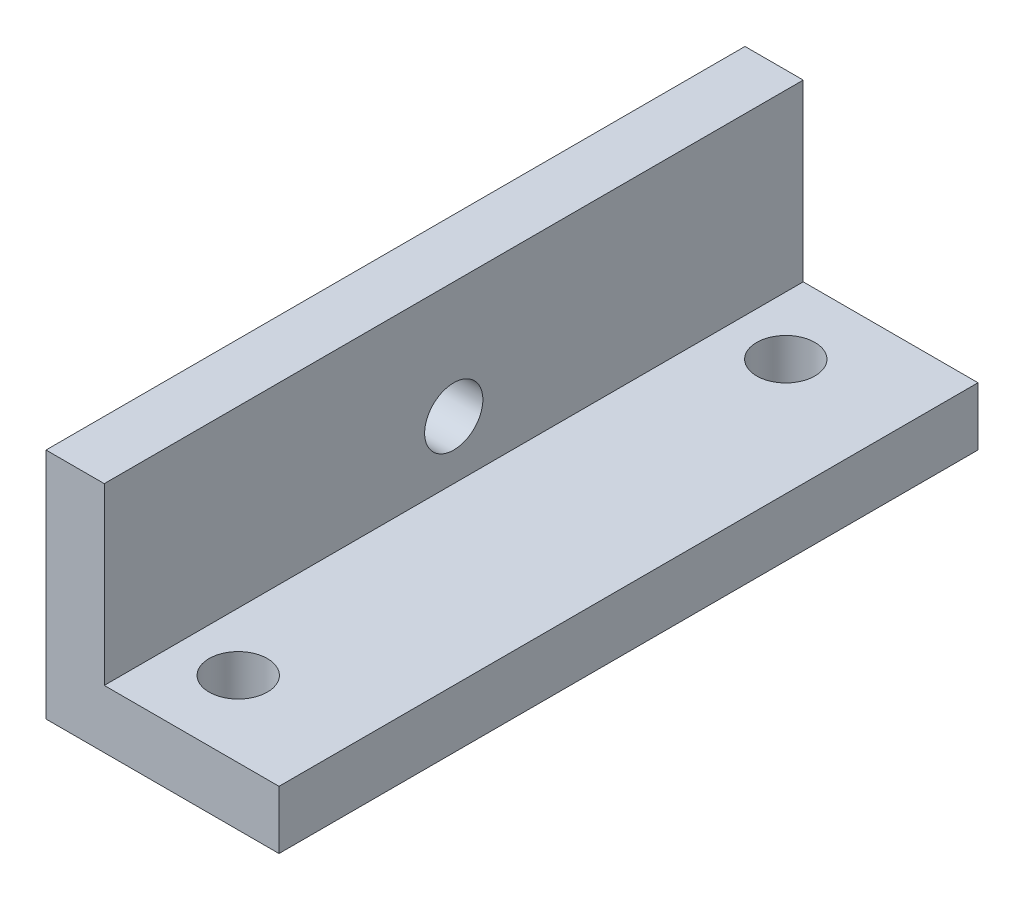
SolidWorks part; units mm, degrees
material "6063-T5"
ref_plane "Front Plane" through (0, 0, 0) normal (0, 0, 1) x (1, 0, 0)
ref_plane "Top Plane" through (0, 0, 0) normal (0, 1, 0) x (1, 0, 0)
ref_plane "Right Plane" through (0, 0, 0) normal (1, 0, 0) x (0, 0, -1)
sketch "Sketch1" plane through (0, 0, 0) normal (0, 0, 1) x (1, 0, 0)
  line L0 (0, 12.7) -> (0, 0)
  line L1 (0, 0) -> (12.7, 0)
  line L2 (0, 12.7) -> (3.175, 12.7)
  line L3 (3.175, 12.7) -> (3.175, 3.175)
  line L4 (3.175, 3.175) -> (12.7, 3.175)
  line L5 (12.7, 3.175) -> (12.7, 0)
  dimension "D1" = 12.7
  dimension "D2" = 12.7
  dimension "D3" = 3.175
  dimension "D4" = 3.175
extrude "Boss-Extrude1" add sketch "Sketch1" along normal blind 38.1
sketch "Sketch2" plane through (0, 0, 0) normal (-1, 0, 0) x (0, 0, 1)
  line L0 (19.05, 12.7) -> (19.05, 0) construction
  line L1 (38.1, 12.7) -> (0, 12.7) construction
  line L2 (38.1, 0) -> (0, 0) construction
  circle A0 centre (19.05, 6.35) radius 1.5875
  dimension "D1" = 3.175
  dimension "D3" = 6.35
extrude "Cut-Extrude1" cut sketch "Sketch2" against normal through all
sketch "Sketch3" plane through (0, 0, 0) normal (0, -1, 0) x (1, 0, 0)
  line L0 (0, 19.05) -> (12.7, 19.05) construction
  line L1 (0, 38.1) -> (0, 0) construction
  line L2 (12.7, 38.1) -> (12.7, 0) construction
  circle A0 centre (6.35, 4.1275) radius 1.5875
  circle A1 centre (6.35, 33.9725) radius 1.5875
  dimension "D1" = 3.175
  dimension "D2" = 6.35
  dimension "D3" = 14.9225
extrude "Cut-Extrude2" cut sketch "Sketch3" against normal through all
